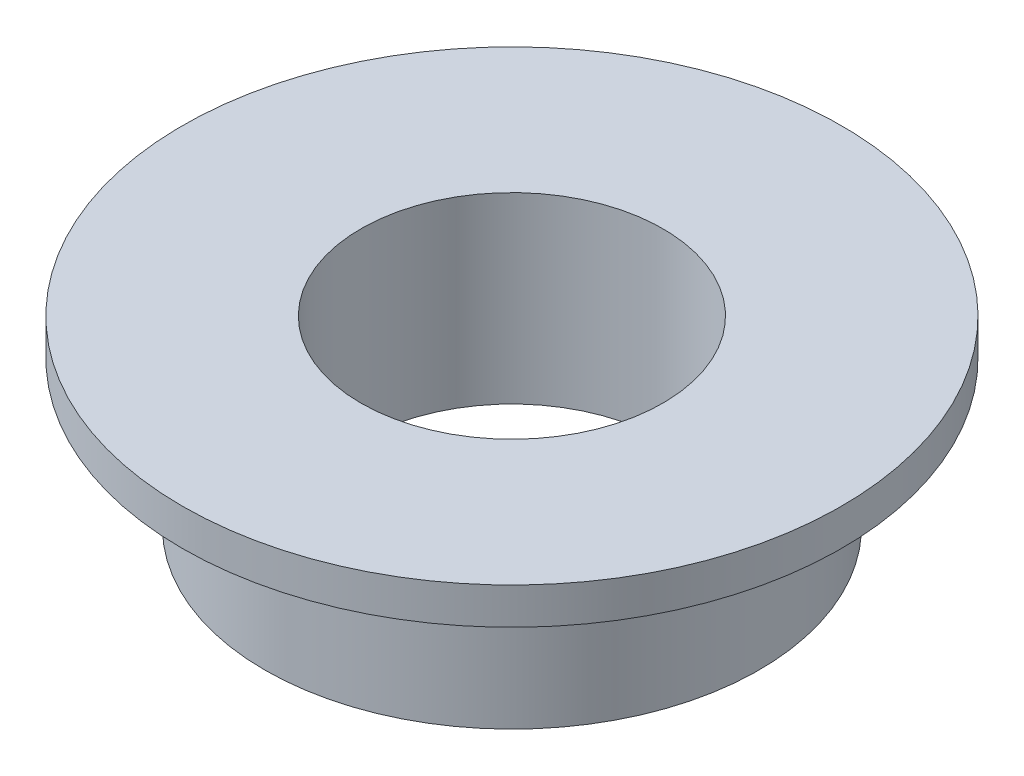
SolidWorks part; units mm, degrees
ref_plane "Front Plane" through (0, 0, 0) normal (0, 0, 1) x (1, 0, 0)
ref_plane "Top Plane" through (0, 0, 0) normal (0, 1, 0) x (1, 0, 0)
ref_plane "Right Plane" through (0, 0, 0) normal (1, 0, 0) x (0, 0, -1)
sketch "Sketch1" plane through (0, 0, 0) normal (0, 1, 0) x (1, 0, 0)
  circle A0 centre (0, 0) radius 6.75
  circle A1 centre (0, 0) radius 4.125
  dimension "D1" = 13.5
  dimension "D2" = 8.25
extrude "Boss-Extrude1" add sketch "Sketch1" along normal blind 4
sketch "Sketch2" plane through (0, 4, 0) normal (0, 1, 0) x (1, 0, 0)
  circle A0 centre (0, 0) radius 4.125 construction
  circle A1 centre (0, 0) radius 4.125
  circle A2 centre (0, 0) radius 9
  dimension "D1" = 18
extrude "Boss-Extrude2" add sketch "Sketch2" along normal blind 1
